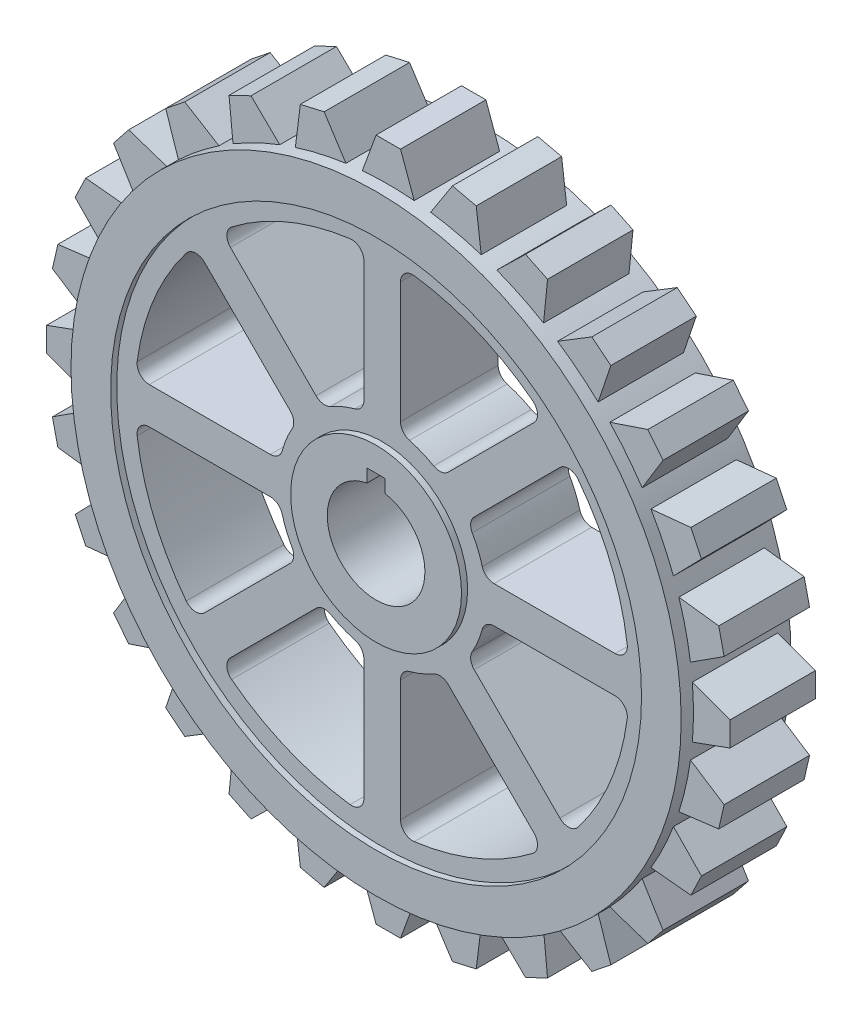
SolidWorks part; units mm, degrees
material "Cast Carbon Steel"
ref_plane "Front Plane" through (0, 0, 0) normal (0, 0, 1) x (1, 0, 0)
ref_plane "Top Plane" through (0, 0, 0) normal (0, 1, 0) x (1, 0, 0)
ref_plane "Right Plane" through (0, 0, 0) normal (1, 0, 0) x (0, 0, -1)
sketch "Sketch1" plane through (0, 0, 0) normal (0, 0, 1) x (1, 0, 0)
  line L0 (-1.5, 7.8581) -> (-1.5, 10)
  line L1 (-1.5, 10) -> (1.5, 10)
  line L2 (1.5, 10) -> (1.5, 7.8581)
  line L3 (0, 0) -> (0, 50) construction
  line L4 (-3, 38.1739) -> (-3, 18.3303)
  line L5 (3, 38.1739) -> (3, 18.3303)
  line L6 (-29.1144, 24.8717) -> (-15.0828, 10.8402)
  line L7 (-24.8717, 29.1144) -> (-10.8402, 15.0828)
  line L8 (-38.1739, -3) -> (-18.3303, -3)
  line L9 (-38.1739, 3) -> (-18.3303, 3)
  line L10 (-24.8717, -29.1144) -> (-10.8402, -15.0828)
  line L11 (-29.1144, -24.8717) -> (-15.0828, -10.8402)
  line L12 (3, -38.1739) -> (3, -18.3303)
  line L13 (-3, -38.1739) -> (-3, -18.3303)
  line L14 (29.1144, -24.8717) -> (15.0828, -10.8402)
  line L15 (24.8717, -29.1144) -> (10.8402, -15.0828)
  line L16 (38.1739, 3) -> (18.3303, 3)
  line L17 (38.1739, -3) -> (18.3303, -3)
  line L18 (24.8717, 29.1144) -> (10.8402, 15.0828)
  line L19 (29.1144, 24.8717) -> (15.0828, 10.8402)
  line L20 (-4.2497, 49.8191) -> (-2, 56)
  line L21 (-2, 56) -> (2, 56)
  line L22 (2, 56) -> (4.2497, 49.8191)
  arc A0 (-1.5, 7.8581) -> (1.5, 7.8581) centre (0, 0) ccw
  circle A1 centre (0, 0) radius 14
  arc A2 (-4.4737, 16.4008) -> (-8.4337, 14.7605) centre (0, 0) ccw
  circle A3 centre (0, 0) radius 43.5
  circle A4 centre (0, 0) radius 50
  arc A6 (-5.2597, 40.157) -> (-24.6761, 32.1145) centre (0, 0) ccw
  arc A7 (3, 18.3303) -> (4.4737, 16.4008) centre (5, 18.3303) ccw
  arc A8 (-3, 18.3303) -> (-4.4737, 16.4008) centre (-5, 18.3303) cw
  arc A9 (3, 38.1739) -> (5.2597, 40.157) centre (5, 38.1739) cw
  arc A10 (-3, 38.1739) -> (-5.2597, 40.157) centre (-5, 38.1739) ccw
  arc A11 (-24.8717, 29.1144) -> (-24.6761, 32.1145) centre (-23.4575, 30.5286) cw
  arc A12 (-29.1144, 24.8717) -> (-32.1145, 24.6761) centre (-30.5286, 23.4575) ccw
  arc A13 (-15.0828, 10.8402) -> (-14.7605, 8.4337) centre (-16.497, 9.4259) cw
  arc A14 (-10.8402, 15.0828) -> (-8.4337, 14.7605) centre (-9.4259, 16.497) ccw
  arc A15 (-38.1739, 3) -> (-40.157, 5.2597) centre (-38.1739, 5) cw
  arc A16 (-38.1739, -3) -> (-40.157, -5.2597) centre (-38.1739, -5) ccw
  arc A17 (-18.3303, -3) -> (-16.4008, -4.4737) centre (-18.3303, -5) cw
  arc A18 (-18.3303, 3) -> (-16.4008, 4.4737) centre (-18.3303, 5) ccw
  arc A19 (-29.1144, -24.8717) -> (-32.1145, -24.6761) centre (-30.5286, -23.4575) cw
  arc A20 (-24.8717, -29.1144) -> (-24.6761, -32.1145) centre (-23.4575, -30.5286) ccw
  arc A21 (-10.8402, -15.0828) -> (-8.4337, -14.7605) centre (-9.4259, -16.497) cw
  arc A22 (-15.0828, -10.8402) -> (-14.7605, -8.4337) centre (-16.497, -9.4259) ccw
  arc A23 (-3, -38.1739) -> (-5.2597, -40.157) centre (-5, -38.1739) cw
  arc A24 (3, -38.1739) -> (5.2597, -40.157) centre (5, -38.1739) ccw
  arc A25 (3, -18.3303) -> (4.4737, -16.4008) centre (5, -18.3303) cw
  arc A26 (-3, -18.3303) -> (-4.4737, -16.4008) centre (-5, -18.3303) ccw
  arc A27 (24.8717, -29.1144) -> (24.6761, -32.1145) centre (23.4575, -30.5286) cw
  arc A28 (29.1144, -24.8717) -> (32.1145, -24.6761) centre (30.5286, -23.4575) ccw
  arc A29 (15.0828, -10.8402) -> (14.7605, -8.4337) centre (16.497, -9.4259) cw
  arc A30 (10.8402, -15.0828) -> (8.4337, -14.7605) centre (9.4259, -16.497) ccw
  arc A31 (38.1739, -3) -> (40.157, -5.2597) centre (38.1739, -5) cw
  arc A32 (38.1739, 3) -> (40.157, 5.2597) centre (38.1739, 5) ccw
  arc A33 (18.3303, 3) -> (16.4008, 4.4737) centre (18.3303, 5) cw
  arc A34 (18.3303, -3) -> (16.4008, -4.4737) centre (18.3303, -5) ccw
  arc A35 (29.1144, 24.8717) -> (32.1145, 24.6761) centre (30.5286, 23.4575) cw
  arc A36 (24.8717, 29.1144) -> (24.6761, 32.1145) centre (23.4575, 30.5286) ccw
  arc A37 (10.8402, 15.0828) -> (8.4337, 14.7605) centre (9.4259, 16.497) cw
  arc A38 (15.0828, 10.8402) -> (14.7605, 8.4337) centre (16.497, 9.4259) ccw
  arc A39 (-32.1145, 24.6761) -> (-40.157, 5.2597) centre (0, 0) ccw
  arc A40 (-14.7605, 8.4337) -> (-16.4008, 4.4737) centre (0, 0) ccw
  arc A41 (8.4337, 14.7605) -> (4.4737, 16.4008) centre (0, 0) ccw
  arc A42 (24.6761, 32.1145) -> (5.2597, 40.157) centre (0, 0) ccw
  arc A43 (40.157, 5.2597) -> (32.1145, 24.6761) centre (0, 0) ccw
  arc A44 (16.4008, 4.4737) -> (14.7605, 8.4337) centre (0, 0) ccw
  arc A45 (14.7605, -8.4337) -> (16.4008, -4.4737) centre (0, 0) ccw
  arc A46 (32.1145, -24.6761) -> (40.157, -5.2597) centre (0, 0) ccw
  arc A47 (4.4737, -16.4008) -> (8.4337, -14.7605) centre (0, 0) ccw
  arc A48 (5.2597, -40.157) -> (24.6761, -32.1145) centre (0, 0) ccw
  arc A49 (-24.6761, -32.1145) -> (-5.2597, -40.157) centre (0, 0) ccw
  arc A50 (-8.4337, -14.7605) -> (-4.4737, -16.4008) centre (0, 0) ccw
  arc A51 (-40.157, -5.2597) -> (-32.1145, -24.6761) centre (0, 0) ccw
  arc A52 (-16.4008, -4.4737) -> (-14.7605, -8.4337) centre (0, 0) ccw
  point P7 (0, 56)
  point P10 (0, 10)
  point P19 (3, 16.7332)
  point P22 (-3, 16.7332)
  point P25 (3, 40.3887)
  point P28 (-3, 40.3887)
  dimension "D1" = 16
  dimension "D4" = 28
  dimension "D7" = 100
  dimension "D8" = 87
  dimension "D11" = 2
  dimension "D2" = 10
  dimension "D3" = 3
  dimension "D5" = 3
  dimension "D9" = 3
  dimension "D10" = 6
  dimension "D12" = 40
  dimension "D6" = 56
  dimension "D13" = 4
extrude "Boss-Extrude1" add sketch "Sketch1" along normal mid plane 18 contours A3 A4 | A0 L0 L1 A1 L2 region at (0, 48.5858, 0) region at (-13.604, 0, 0)
extrude "Boss-Extrude2" add sketch "Sketch1<4>" along normal mid plane 16 contours A1 A3 A48 A24 L12 A25 A47 A30 L15 A27 A46 A28 L14 A29 A45 A34 L17 A31 A42 A36 L18 A37 A41 A7 L5 A9 A14 L7 A11 A6 A10 L4 A8 A2 A13 A40 A18 L9 A15 A39 A12 L6 A33 region at (-42.2696, 0, 0)
sketch "Sketch1<4>" plane through (0, 0, 0) normal (0, 0, 1) x (1, 0, 0) same geometry as "Sketch1"
extrude "Boss-Extrude3" add sketch "Sketch1<5>" along normal mid plane 14 contours A4 L22 L21 L20 region at (0, 52.6109, 0)
sketch "Sketch1<5>" plane through (0, 0, 0) normal (0, 0, 1) x (1, 0, 0) same geometry as "Sketch1"
sketch "Sketch2" plane through (0, 0, 0) normal (1, 0, 0) x (0, 0, -1)
  line L0 (-9, 0) -> (9, 0) construction
  line L1 (9, -50) -> (9, 50) construction
  point P6 (0, 0)
pattern_circular "CirPattern1" count 28 over 360 about axis through (0, 0, 9) along (0, 0, -1) of "Boss-Extrude3"
equation "\"A\" = 112"
equation "\"B\" = 28"
equation "\"C\"= 3"
equation "\"D5@Sketch1\"=\"C\""
equation "\"D7@Sketch1\"=\"A\"-12"
equation "\"D8@Sketch1\"=\"D7@Sketch1\"-13"
equation "\"D9@Sketch1\"=\"C\""
equation "\"D10@Sketch1\"=\"C\"*2"
equation "\"D6@Sketch1\"=\"A\"/2"
equation "\"D1@CirPattern1\"=\"B\""
